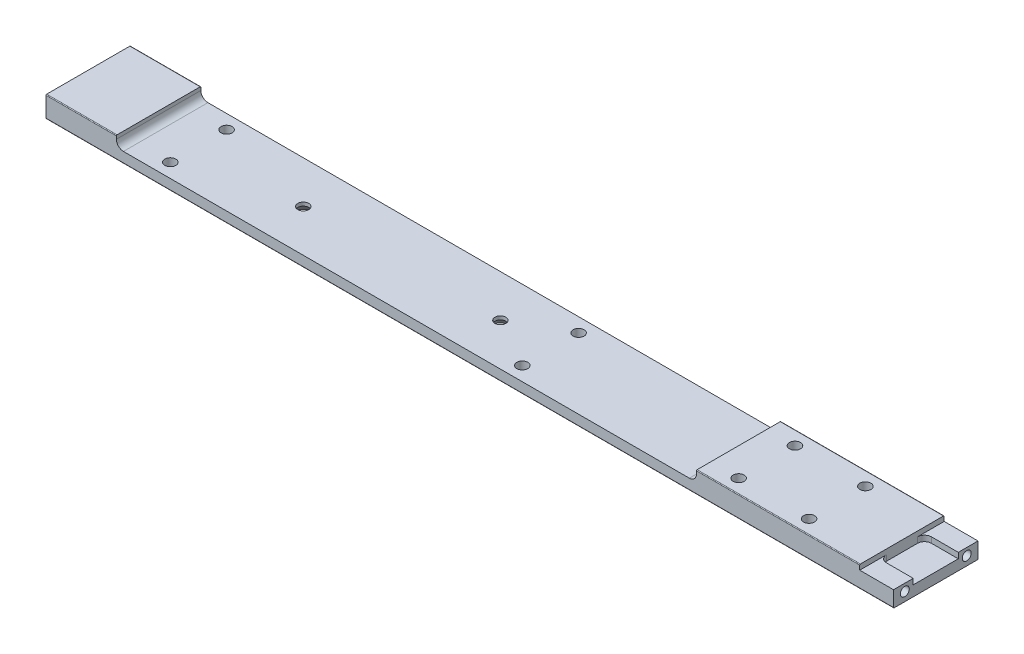
SolidWorks part; units mm, degrees
material "6061 Alloy"
ref_plane "Front Plane" through (0, 0, 0) normal (0, 0, 1) x (1, 0, 0)
ref_plane "Top Plane" through (0, 0, 0) normal (0, 1, 0) x (1, 0, 0)
ref_plane "Right Plane" through (0, 0, 0) normal (1, 0, 0) x (0, 0, -1)
sketch "Sketch1" plane through (0, 0, 0) normal (0, 1, 0) x (1, 0, 0)
  line L1 (191.135, -19.05) -> (-191.135, -19.05)
  line L2 (191.135, -19.05) -> (191.135, 19.05)
  line L3 (191.135, 19.05) -> (-191.135, 19.05)
  line L4 (-191.135, -19.05) -> (-191.135, 19.05)
  line L5 (191.135, -19.05) -> (-191.135, 19.05) construction
  line L6 (191.135, 19.05) -> (-191.135, -19.05) construction
  point P0 (0, 0)
  dimension "Length" = 382.27
  dimension "Width" = 38.1
sketch "Sketch2" plane through (0, 0, 0) normal (1, 0, 0) x (0, 0, -1)
  line L0 (19.05, 4.7625) -> (19.05, -4.7625) construction
  point P2 (19.05, 0)
  dimension "Thickness" = 9.525
sketch "Sketch3" plane through (0, 0, 0) normal (0, 1, 0) x (1, 0, 0)
  line L1 (-191.135, 19.05) -> (191.135, 19.05)
  line L2 (-191.135, 19.05) -> (-191.135, -19.05)
  line L3 (-191.135, -19.05) -> (191.135, -19.05)
  line L4 (191.135, 19.05) -> (191.135, -19.05)
extrude "Boss-Extrude1" add sketch "Sketch3" against normal up to vertex (4.7625 mm away) and the other way up to vertex (4.7625 mm away) up to point (0, -4.7625, -19.05) other way up to point (0, 4.7625, -19.05)
fillet "Fillet1" radius 0.3143 4 edges at (0, -4.7625, 19.05) (0, -4.7625, -19.05) (0, 4.7625, -19.05) (0, 4.7625, 19.05)
sketch "Sketch4" plane through (-191.135, 0, 0) normal (-1, 0, 0) x (0, 0, 1)
  line L0 (0, -0.762) -> (13.97, -0.762) construction
  line L1 (0, -0.762) -> (-13.97, -0.762) construction
  line L2 (0, -0.762) -> (0, 0) construction
  dimension "D1" = 13.97
  dimension "D2" = 13.97
  dimension "D3" = 0.762
hole_wizard "Tap Drill for #10-32 Tap1" positions "Sketch5" profile "Sketch6" hole size "#10-32" standard "ANSI Inch"
sketch "Sketch5" plane through (-191.135, 0, 0) normal (-1, 0, 0) x (0, 0, 1)
  point P0 (-13.97, -0.762)
  point P3 (13.97, -0.762)
sketch "Sketch6" plane through (-191.135, -0.762, -13.97) normal (0, 1, 0) x (0, 0, 1)
  line L0 (0, 0) -> (0, 26.6133)
  line L1 (0, 26.6133) -> (2.0193, 25.4)
  line L2 (2.0193, 25.4) -> (2.0193, 0)
  line L5 (2.0193, 0) -> (0, 0)
  line L10 (0, 26.6133) -> (-2.0193, 25.4) construction
  line L11 (0, -6.35) -> (0, 107.95) construction
  dimension "Hole Dia." = 4.0386
  dimension "Hole Depth" = 25.4
  dimension "Drill Angle" = 118
hole_wizard "Tap Drill for #10-32 Tap2" positions "Sketch7" profile "Sketch8" hole size "#10-32" standard "ANSI Inch"
sketch "Sketch7" plane through (191.135, 0, 0) normal (1, 0, 0) x (0, 0, -1)
  point P0 (-13.97, -0.762)
  point P3 (13.97, -0.762)
sketch "Sketch8" plane through (191.135, -0.762, 13.97) normal (0, 1, 0) x (0, 0, -1)
  line L0 (0, 0) -> (0, 26.6133)
  line L1 (0, 26.6133) -> (2.0193, 25.4)
  line L2 (2.0193, 25.4) -> (2.0193, 0)
  line L5 (2.0193, 0) -> (0, 0)
  line L10 (0, 26.6133) -> (-2.0193, 25.4) construction
  line L11 (0, -6.35) -> (0, 107.95) construction
  dimension "Hole Dia." = 4.0386
  dimension "Hole Depth" = 25.4
  dimension "Drill Angle" = 118
sketch "Sketch10" plane through (0, 0, -19.05) normal (0, 0, -1) x (-1, 0, 0)
  line L0 (159.385, 4.7625) -> (159.385, 3.175)
  line L1 (-191.135, 4.7625) -> (191.135, 4.7625) construction
  line L2 (156.21, 0) -> (-99.06, 0)
  line L3 (-102.235, 3.175) -> (-102.235, 4.7625)
  line L4 (-102.235, 4.7625) -> (159.385, 4.7625)
  line L5 (-191.135, -3.175) -> (-191.135, 33.0219) construction
  line L6 (191.135, -3.175) -> (191.135, 33.0219) construction
  line L7 (-191.135, 4.7625) -> (-175.895, 4.7625)
  line L8 (-175.895, 4.7625) -> (-175.895, 2.4765)
  line L9 (-175.895, 2.4765) -> (-191.135, 2.4765)
  line L10 (-191.135, -4.4482) -> (-191.135, 4.4482) construction
  line L11 (-191.135, 2.4765) -> (-191.135, 4.7625)
  arc A0 (159.385, 3.175) -> (156.21, 0) centre (156.21, 3.175) cw
  arc A1 (-99.06, 0) -> (-102.235, 3.175) centre (-99.06, 3.175) cw
  point P12 (159.385, 0)
  dimension "D4" = 3.175
  dimension "D1" = 88.9
  dimension "D2" = 31.75
  dimension "D3" = 4.7625
  dimension "D5" = 15.24
  dimension "D6" = 2.286
extrude "Cut-Extrude1" cut sketch "Sketch10" against normal through all
sketch "Sketch13" plane through (0, -4.7625, 0) normal (0, -1, 0) x (1, 0, 0)
  line L0 (191.135, 0) -> (146.685, 0) construction
  line L1 (191.135, 18.7357) -> (191.135, -18.7357) construction
  line L2 (146.685, 0) -> (146.685, 12.7) construction
  line L3 (146.685, 12.7) -> (114.935, 12.7) construction
  line L4 (114.935, 12.7) -> (114.935, -12.7) construction
  line L5 (114.935, -12.7) -> (146.685, -12.7) construction
  line L6 (146.685, -12.7) -> (146.685, 0) construction
  dimension "D1" = 44.45
  dimension "D2" = 31.75
  dimension "D3" = 31.75
hole_wizard "#10 Clearance Hole1" positions "Sketch14" profile "Sketch15" hole size "#10" standard "ANSI Inch" end condition through all
sketch "Sketch14" plane through (0, -4.7625, 0) normal (0, -1, 0) x (-1, 0, 0)
  point P0 (-114.935, 12.7)
  point P3 (-146.685, 12.7)
  point P6 (-146.685, -12.7)
  point P9 (-114.935, -12.7)
sketch "Sketch15" plane through (114.935, -4.7625, -12.7) normal (1, 0, 0) x (0, 0, -1)
  line L0 (0, 0) -> (0, 9.525)
  line L1 (0, 9.525) -> (2.4892, 9.525)
  line L2 (2.4892, 9.525) -> (2.4892, 3.1411)
  line L3 (2.4892, 3.1411) -> (5.2197, 0)
  line L5 (5.2197, 0) -> (0, 0)
  line L6 (-2.4892, 3.1411) -> (-5.2197, 0) construction
  line L11 (0, -6.35) -> (0, 107.95) construction
  dimension "Thru Hole Dia." = 4.9784
  dimension "Thru Hole Depth" = 9.525
  dimension "Near C'Sink Dia." = 10.4394
  dimension "Near C'Sink Angle" = 82
sketch "Sketch17" plane through (0, 2.4765, 0) normal (0, 1, 0) x (1, 0, 0)
  line L23 (191.135, 0) -> (191.135, 10.16)
  line L24 (191.135, -19.05) -> (191.135, 19.05) construction
  line L25 (191.135, 10.16) -> (179.07, 10.16)
  line L27 (175.895, 6.985) -> (175.895, -6.985)
  line L28 (179.07, -10.16) -> (191.135, -10.16)
  line L29 (191.135, -10.16) -> (191.135, 0)
  arc A0 (175.895, -6.985) -> (179.07, -10.16) centre (179.07, -6.985) ccw
  arc A1 (179.07, 10.16) -> (175.895, 6.985) centre (179.07, 6.985) ccw
  point P11 (175.895, 10.16)
  dimension "D2" = 3.175
  dimension "D1" = 15.24
extrude "Cut-Extrude2" cut sketch "Sketch17" against normal blind 2.54
sketch "Sketch18" plane through (0, 0, 0) normal (0, 1, 0) x (1, 0, 0)
  line L0 (30.0312, 19.05) -> (17.3312, 19.05) construction
  line L1 (99.06, 19.05) -> (-156.21, 19.05) construction
  line L2 (30.0312, 19.584) -> (30.0312, 16.7333) construction
  line L3 (17.3312, 19.05) -> (17.3312, 12.7) construction
  line L4 (17.3312, 12.7) -> (17.3312, -12.7) construction
  line L5 (17.3312, -12.7) -> (17.3312, -19.05) construction
  line L6 (99.06, -19.05) -> (-156.21, -19.05) construction
  line L7 (17.3312, -19.05) -> (-141.4188, -19.05) construction
  line L8 (-141.4188, -19.05) -> (-141.4188, -12.7) construction
  line L9 (-141.4188, -12.7) -> (-141.4188, 12.7) construction
  line L10 (-141.4188, 12.7) -> (-141.4188, 19.05) construction
  dimension "D1" = 6.35
  dimension "D2" = 25.4
  dimension "D3" = 6.35
  dimension "D4" = 25.4
hole_wizard "#10 Clearance Hole2" positions "Sketch19" profile "Sketch20" hole size "#10" standard "ANSI Inch" end condition through all
sketch "Sketch19" plane through (0, 0, 0) normal (0, 1, 0) x (1, 0, 0)
  point P0 (-141.4188, 12.7)
  point P3 (-141.4188, -12.7)
  point P6 (17.3312, 12.7)
  point P9 (17.3312, -12.7)
sketch "Sketch20" plane through (-141.4188, 0, -12.7) normal (1, 0, 0) x (0, 0, 1)
  line L0 (0, 0) -> (0, 4.7625)
  line L1 (0, 4.7625) -> (2.4892, 4.7625)
  line L2 (2.4892, 4.7625) -> (2.4892, 0)
  line L5 (2.4892, 0) -> (0, 0)
  line L11 (0, -6.35) -> (0, 107.95) construction
  dimension "Thru Hole Dia." = 4.9784
  dimension "Thru Hole Depth" = 4.7625
sketch "Sketch21" plane through (191.135, 0, 0) normal (1, 0, 0) x (0, 0, -1)
  circle A0 centre (0, 33.0219) radius 31.75 construction
hole_wizard "#10 (0.1935) Diameter Hole1" positions "Sketch22" profile "Sketch23" hole size "#10" standard "ANSI Inch" end condition through all
sketch "Sketch22" plane through (0, -4.7625, 0) normal (0, -1, 0) x (-1, 0, 0)
  point P0 (94.1337, 0)
  point P3 (5.2337, 0)
sketch "Sketch23" plane through (-94.1337, -4.7625, 0) normal (1, 0, 0) x (0, 0, -1)
  line L0 (0, 0) -> (0, 9.525)
  line L1 (0, 9.525) -> (2.4574, 9.525)
  line L2 (2.4574, 9.525) -> (2.4574, 3.1776)
  line L3 (2.4574, 3.1776) -> (5.2197, 0)
  line L5 (5.2197, 0) -> (0, 0)
  line L6 (-2.4574, 3.1776) -> (-5.2197, 0) construction
  line L11 (0, -6.35) -> (0, 107.95) construction
  dimension "Thru Hole Dia." = 4.9149
  dimension "Thru Hole Depth" = 9.525
  dimension "Near C'Sink Dia." = 10.4394
  dimension "Near C'Sink Angle" = 82
equation "\"D1@Fillet1\" = \"Thickness@Sketch2\" * .033"
